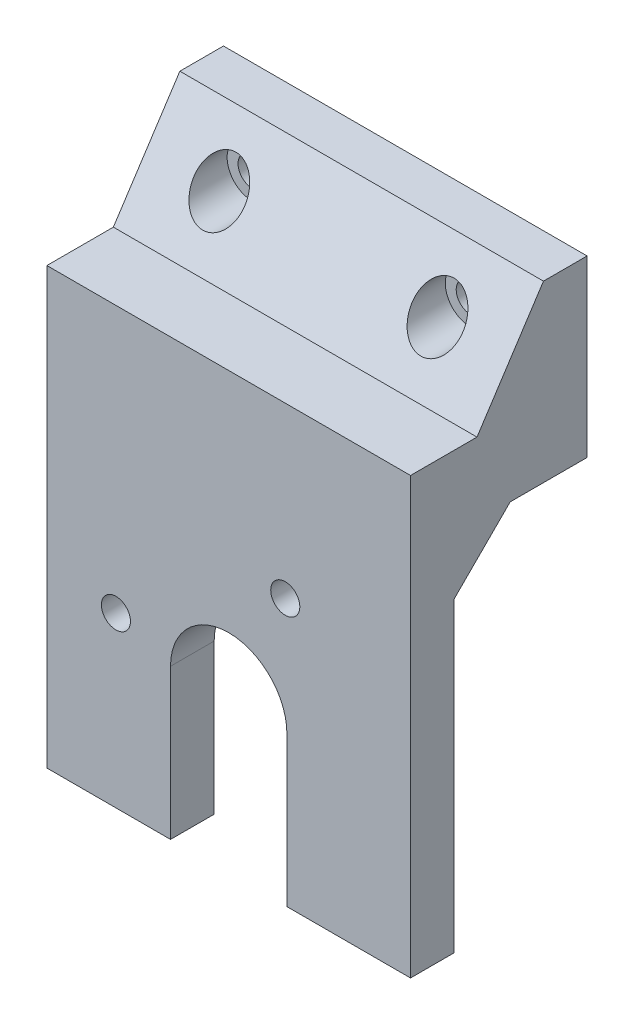
SolidWorks part; units mm, degrees
material "ABS"
ref_plane "Front Plane" through (0, 0, 0) normal (0, 0, 1) x (1, 0, 0)
ref_plane "Top Plane" through (0, 0, 0) normal (0, 1, 0) x (1, 0, 0)
ref_plane "Right Plane" through (0, 0, 0) normal (1, 0, 0) x (0, 0, -1)
sketch "Sketch1" plane through (0, 0, 0) normal (0, 0, 1) x (1, 0, 0)
  line L1 (-37.3941, 10.9555) -> (12.6059, 10.9555)
  line L2 (-37.3941, 10.9555) -> (-37.3941, -7.0445)
  line L3 (-37.3941, -7.0445) -> (12.6059, -7.0445)
  line L4 (12.6059, 10.9555) -> (12.6059, -7.0445)
  dimension "D1" = 50
  dimension "D2" = 18
extrude "Boss-Extrude1" add sketch "Sketch1" along normal blind 7
sketch "Sketch2" plane through (0, 0, 7) normal (0, 0, 1) x (1, 0, 0)
  line L0 (12.6059, -7.0445) -> (12.6059, 10.9555) construction
  line L1 (-37.3941, 10.9555) -> (12.6059, 10.9555)
  line L2 (-37.3941, 10.9555) -> (-37.3941, 2.9555)
  line L3 (-37.3941, 2.9555) -> (12.6059, 2.9555)
  line L4 (12.6059, 10.9555) -> (12.6059, 2.9555)
  dimension "D1" = 8
extrude "Boss-Extrude2" add sketch "Sketch2" along normal blind 6.7
sketch "Sketch3" plane through (12.6059, 0, 0) normal (1, 0, 0) x (0, 0, -1)
  line L0 (-13.7, 10.9555) -> (0, 10.9555) construction
  line L1 (-7, 2.9555) -> (0, 2.9555)
  line L2 (-7, 2.9555) -> (-7, 10.9555)
  line L3 (-7, 10.9555) -> (0, 10.9555)
  line L4 (0, 2.9555) -> (0, 10.9555)
extrude "Boss-Extrude3" add sketch "Sketch3" along normal blind 23
sketch "Sketch4" plane through (-37.3941, 0, 0) normal (-1, 0, 0) x (0, 0, 1)
  line L1 (7, 2.9555) -> (0, 2.9555)
  line L2 (7, 2.9555) -> (7, 10.9555)
  line L3 (7, 10.9555) -> (0, 10.9555)
  line L4 (0, 2.9555) -> (0, 10.9555)
extrude "Boss-Extrude4" add sketch "Sketch4" along normal blind 14
sketch "Sketch5" plane through (0, 0, 7) normal (0, 0, 1) x (1, 0, 0)
  line L1 (-37.3941, -7.0445) -> (12.6059, -7.0445)
  line L2 (-37.3941, -7.0445) -> (-37.3941, 2.9555)
  line L3 (-37.3941, 2.9555) -> (12.6059, 2.9555)
  line L4 (12.6059, -7.0445) -> (12.6059, 2.9555)
extrude "Cut-Extrude1" cut sketch "Sketch5" against normal blind 14
sketch "Sketch6" plane through (0, 0, 7) normal (0, 0, 1) x (1, 0, 0)
  line L0 (35.6059, 10.9555) -> (35.6059, 2.9555) construction
  line L2 (-51.3941, 2.9555) -> (-37.3941, 2.9555) construction
  line L3 (35.6059, 2.9555) -> (12.6059, 2.9555) construction
  circle A0 centre (19.6059, 6.9555) radius 2
  circle A1 centre (28.6059, 6.9555) radius 2
  dimension "D1" = 4
  dimension "D2" = 4
  dimension "D3" = 7
  dimension "D4" = 9
  dimension "D5" = 4
  dimension "D6" = 4
extrude "Cut-Extrude2" cut sketch "Sketch6" against normal blind 14
sketch "Sketch7" plane through (0, 2.9555, 0) normal (0, -1, 0) x (1, 0, 0)
  line L0 (12.6059, 13.7) -> (12.6059, 7) construction
  line L1 (-37.3941, 13.7) -> (12.6059, 13.7)
  line L2 (-37.3941, 13.7) -> (-37.3941, 7.7)
  line L3 (-37.3941, 7.7) -> (12.6059, 7.7)
  line L4 (12.6059, 13.7) -> (12.6059, 7.7)
  dimension "D1" = 6
extrude "Boss-Extrude5" add sketch "Sketch7" along normal blind 67.91
sketch "Sketch8" plane through (0, 0, 13.7) normal (0, 0, 1) x (1, 0, 0)
  line L0 (-12.3941, -44.3312) -> (-12.3941, -64.9545) construction
  line L1 (12.6059, -64.9545) -> (-37.3941, -64.9545) construction
  line L2 (-4.3941, -44.3312) -> (-4.3941, -64.9545)
  line L3 (-20.3941, -44.3312) -> (-20.3941, -64.9545)
  line L4 (-37.3941, 10.9555) -> (-37.3941, -64.9545) construction
  arc A0 (-4.3941, -44.3312) -> (-20.3941, -44.3312) centre (-12.3941, -44.3312) ccw
  arc A1 (-20.3941, -64.9545) -> (-4.3941, -64.9545) centre (-12.3941, -64.9545) ccw
  point P4 (-12.3941, -54.6428)
  dimension "D3" = 20.6233
  dimension "D1" = 16
  dimension "D2" = 25
extrude "Cut-Extrude3" cut sketch "Sketch8" against normal blind 35
sketch "Sketch9" plane through (0, 0, 7.7) normal (0, 0, -1) x (-1, 0, 0)
  line L0 (-12.6059, -64.9545) -> (4.3941, -64.9545) construction
  line L1 (20.3941, -64.9545) -> (37.3941, -64.9545) construction
  circle A0 centre (27.901, -41.7569) radius 2
  circle A1 centre (4.6167, -28.3707) radius 2
  dimension "D1" = 4
  dimension "D2" = 4
  dimension "D3" = 36.5838
  dimension "D4" = 23.1976
extrude "Cut-Extrude5" cut sketch "Sketch9" against normal blind 35
sketch "Sketch13" plane through (0, 0, 7) normal (0, 0, 1) x (1, 0, 0)
  line L1 (-51.3941, 10.9555) -> (-37.3941, 10.9555)
  line L2 (-51.3941, 10.9555) -> (-51.3941, 2.9555)
  line L3 (-51.3941, 2.9555) -> (-37.3941, 2.9555)
  line L4 (-37.3941, 10.9555) -> (-37.3941, 2.9555)
extrude "Cut-Extrude6" cut sketch "Sketch13" against normal blind 10
sketch "Sketch14" plane through (-37.3941, 0, 0) normal (-1, 0, 0) x (0, 0, 1)
  line L1 (7.7, 2.9555) -> (0, 2.9555)
  line L2 (7.7, 2.9555) -> (7.7, 10.9555)
  line L3 (7.7, 10.9555) -> (0, 10.9555)
  line L4 (0, 2.9555) -> (0, 10.9555)
extrude "Cut-Extrude7" cut sketch "Sketch14" against normal blind 120
sketch "Sketch15" plane through (0, 0, 7.7) normal (0, 0, -1) x (-1, 0, 0)
  line L0 (-12.6059, -64.9545) -> (-12.6059, 10.9555) construction
  line L1 (37.3941, 10.9555) -> (-12.6059, 10.9555)
  line L2 (37.3941, 10.9555) -> (37.3941, -3.0445)
  line L3 (37.3941, -3.0445) -> (-12.6059, -3.0445)
  line L4 (-12.6059, 10.9555) -> (-12.6059, -3.0445)
  dimension "D1" = 14
extrude "Boss-Extrude6" add sketch "Sketch15" along normal blind 6.4
sketch "Sketch16" plane through (0, 0, 13.7) normal (0, 0, 1) x (1, 0, 0)
  line L0 (-37.3941, 10.9555) -> (-37.3941, -64.9545) construction
  line L1 (12.6059, 10.9555) -> (-37.3941, 10.9555)
  line L2 (12.6059, 10.9555) -> (12.6059, -3.0445)
  line L3 (12.6059, -3.0445) -> (-37.3941, -3.0445)
  line L4 (-37.3941, 10.9555) -> (-37.3941, -3.0445)
  dimension "D1" = 14
extrude "Cut-Extrude8" cut sketch "Sketch16" against normal up to vertex (6 mm away) up to point (-37.3941, -3.0445, 7.7)
sketch "Sketch17" plane through (-37.3941, 0, 0) normal (-1, 0, 0) x (0, 0, 1)
  line L0 (13.7, -3.0445) -> (7.7, -3.0445)
  line L1 (7.7, -3.0445) -> (7.7, 10.9555)
  line L2 (7.7, 10.9555) -> (13.7, -3.0445)
  line L3 (7.7, -3.0445) -> (1.3, -3.0445)
  line L4 (1.3, -3.0445) -> (7.7, -3.0445) construction
  line L5 (1.3, -3.0445) -> (7.7, -14.7804)
  line L6 (7.7, -64.9545) -> (7.7, -3.0445) construction
  line L7 (7.7, -14.7804) -> (7.7, -3.0445)
  line M1 (1.3, -3.0445) -> (7.7, -3.0445)
  line M2 (7.7, -3.0445) -> (7.7, 10.9555)
extrude "Boss-Extrude7" add sketch "Sketch17" against normal blind 50 contours L2 L0 M2 | L5 L7 M1 region at (-37.3941, -6.9565, 5.5667) region at (-37.3941, 1.6222, 9.7)
sketch "Sketch18" plane through (0, 0, 1.3) normal (0, 0, -1) x (-1, 0, 0)
  line L0 (-12.6059, 10.9555) -> (-12.6059, -3.0445) construction
  line L1 (37.3941, 10.9555) -> (-12.6059, 10.9555) construction
  circle A0 centre (-5.6059, 3.9555) radius 2
  circle A1 centre (30.3941, 4.9553) radius 2
  dimension "D1" = 4
  dimension "D2" = 4
  dimension "D3" = 36
  dimension "D4" = 7
  dimension "D5" = 7
extrude "Cut-Extrude9" cut sketch "Sketch18" against normal blind 6.4
sketch "Sketch19" plane through (0, 0, 7.7) normal (0, 0, -1) x (-1, 0, 0)
  circle A0 centre (30.3941, 4.9553) radius 3.5
  circle A1 centre (-5.6059, 3.9555) radius 3.5
  dimension "D1" = 7
  dimension "D2" = 7
extrude "Cut-Extrude10" cut sketch "Sketch19" against normal blind 6.4
sketch "Sketch20" plane through (-37.3941, 0, 0) normal (-1, 0, 0) x (0, 0, 1)
  line L0 (13.7, -3.0445) -> (13.7, -64.9545) construction
  line L1 (1.3, 10.9555) -> (13.7, 10.9555)
  line L2 (1.3, 10.9555) -> (1.3, -15.1123)
  line L3 (1.3, -15.1123) -> (13.7, -15.1123)
  line L4 (13.7, 10.9555) -> (13.7, -15.1123)
extrude "Cut-Extrude11" cut sketch "Sketch20" against normal blind 70
sketch "Sketch21" plane through (0, -15.1123, 0) normal (0, 1, 0) x (1, 0, 0)
  line L1 (12.6059, -13.7) -> (-37.3941, -13.7)
  line L2 (12.6059, -13.7) -> (12.6059, -7.7)
  line L3 (12.6059, -7.7) -> (-37.3941, -7.7)
  line L4 (-37.3941, -13.7) -> (-37.3941, -7.7)
extrude "Boss-Extrude8" add sketch "Sketch21" along normal blind 10
sketch "Sketch22" plane through (0, 0, 7.7) normal (0, 0, -1) x (-1, 0, 0)
  line L1 (37.3941, -5.1123) -> (-12.6059, -5.1123)
  line L2 (37.3941, -5.1123) -> (37.3941, -15.1123)
  line L3 (37.3941, -15.1123) -> (-12.6059, -15.1123)
  line L4 (-12.6059, -5.1123) -> (-12.6059, -15.1123)
  dimension "D1" = 10
extrude "Boss-Extrude9" add sketch "Sketch22" along normal blind 18.28
sketch "Sketch23" plane through (0, -5.1123, 0) normal (0, 1, 0) x (1, 0, 0)
  line L0 (-37.3941, 10.58) -> (-37.3941, -13.7) construction
  line L1 (12.6059, 10.58) -> (-37.3941, 10.58)
  line L2 (12.6059, 10.58) -> (12.6059, 4.58)
  line L3 (12.6059, 4.58) -> (-37.3941, 4.58)
  line L4 (-37.3941, 10.58) -> (-37.3941, 4.58)
  dimension "D1" = 6
extrude "Boss-Extrude10" add sketch "Sketch23" along normal blind 14
sketch "Sketch24" plane through (0, 0, -4.58) normal (0, 0, 1) x (1, 0, 0)
  line L1 (12.6059, 8.8877) -> (12.6059, -5.1123) construction
  line L2 (-37.3941, 8.8877) -> (-37.3941, -5.1123) construction
  line L3 (-37.3941, 8.8877) -> (12.6059, 8.8877) construction
  circle A0 centre (2.6059, 1.8877) radius 2
  circle A1 centre (-27.3941, 1.8877) radius 2
  dimension "D1" = 4
  dimension "D2" = 4
  dimension "D3" = 10
  dimension "D4" = 10
  dimension "D5" = 7
  dimension "D6" = 0
extrude "Cut-Extrude12" cut sketch "Sketch24" against normal blind 14
sketch "Sketch25" plane through (-37.3941, 0, 0) normal (-1, 0, 0) x (0, 0, 1)
  line L0 (7.7, -15.1123) -> (0, -15.1123)
  line L1 (-10.58, -15.1123) -> (7.7, -15.1123) construction
  line L2 (0, -15.1123) -> (7.7, -22.8123)
  line L3 (7.7, -64.9545) -> (7.7, -15.1123) construction
  line L4 (7.7, -22.8123) -> (7.7, -15.1123)
  line L5 (-4.58, -5.1123) -> (4.56, -5.1123)
  line L6 (-4.58, -5.1123) -> (13.7, -5.1123) construction
  line L7 (4.56, -5.1123) -> (-4.58, 8.8877)
  line L8 (-4.58, 8.8877) -> (-4.58, -5.1123)
extrude "Boss-Extrude11" add sketch "Sketch25" against normal up to vertex (50 mm away) up to point (12.6059, -15.1123, 7.7)
sketch "Sketch26" plane through (0, 0, -4.58) normal (0, 0, -1) x (-1, 0, 0)
  circle A0 centre (27.3941, 1.8877) radius 3.5
  circle A1 centre (-2.6059, 1.8877) radius 3.5
  dimension "D1" = 7
  dimension "D2" = 7
extrude "Cut-Extrude13" cut sketch "Sketch26" against normal blind 14
